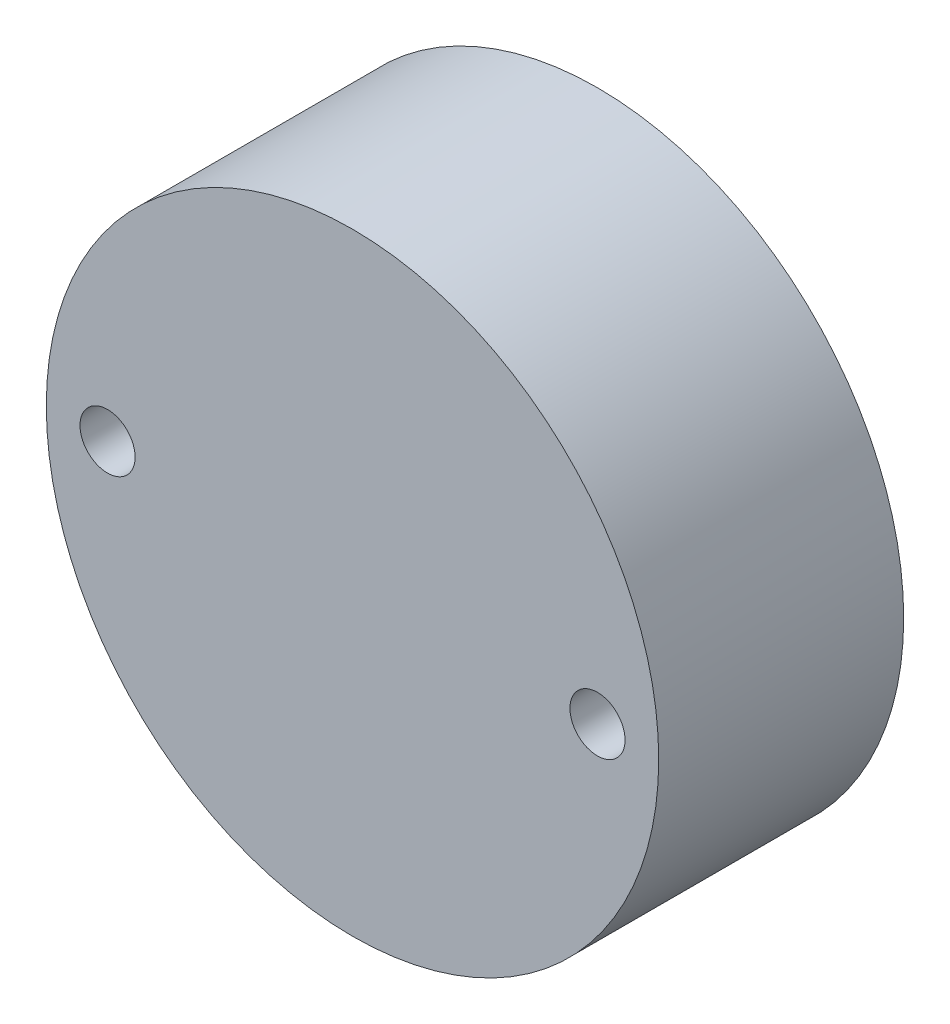
SolidWorks part; units mm, degrees
ref_plane "Front Plane" through (0, 0, 0) normal (0, 0, 1) x (1, 0, 0)
ref_plane "Top Plane" through (0, 0, 0) normal (0, 1, 0) x (1, 0, 0)
ref_plane "Right Plane" through (0, 0, 0) normal (1, 0, 0) x (0, 0, -1)
sketch "Sketch1" plane through (0, 0, 0) normal (0, 0, 1) x (1, 0, 0)
  circle A0 centre (215, -6) radius 2.25 construction
  circle A1 centre (235, -6) radius 25 construction
  circle A2 centre (255, -6) radius 2.25 construction
  circle A3 centre (215, -6) radius 2.25
  circle A4 centre (235, -6) radius 25
  circle A5 centre (255, -6) radius 2.25
extrude "Boss-Extrude1" add sketch "Sketch1" along normal up to surface (20 mm away)
